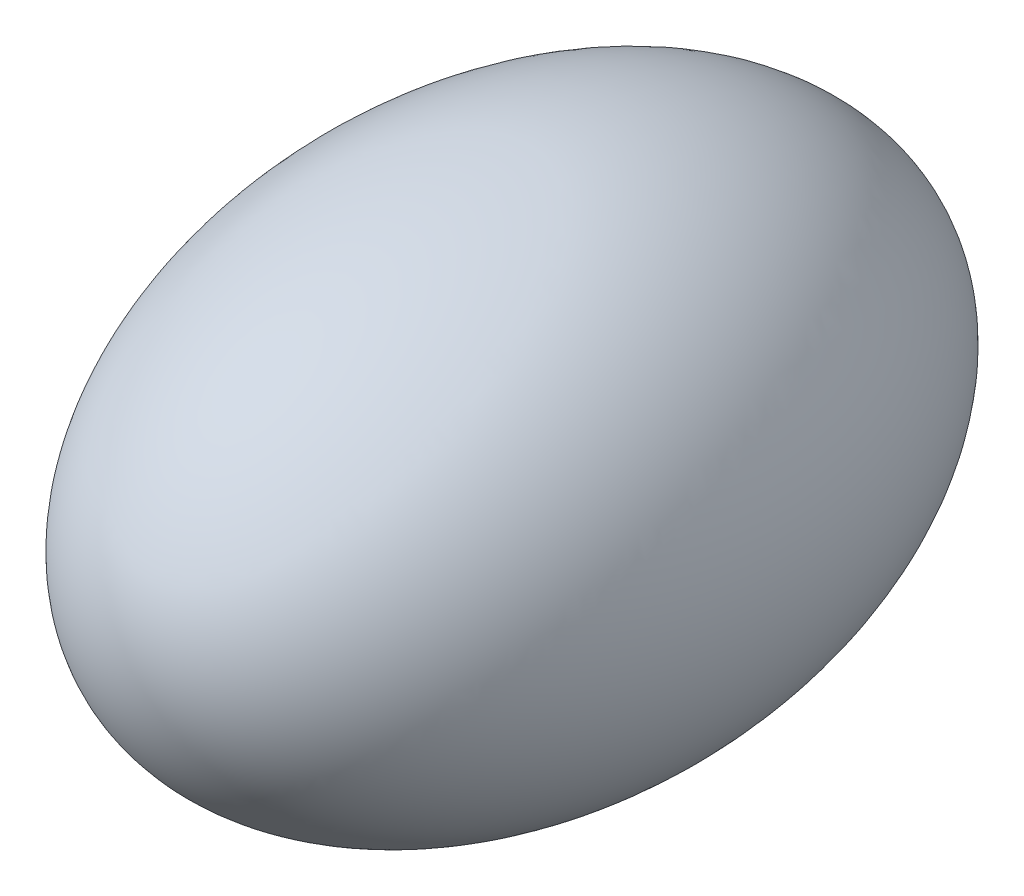
SolidWorks part; units mm, degrees
ref_plane "Front Plane" through (0, 0, 0) normal (0, 0, 1) x (1, 0, 0)
ref_plane "Top Plane" through (0, 0, 0) normal (0, 1, 0) x (1, 0, 0)
ref_plane "Right Plane" through (0, 0, 0) normal (1, 0, 0) x (0, 0, -1)
sketch "Sketch1" plane through (0, 0, 0) normal (0, 1, 0) x (1, 0, 0)
  line L0 (0, 75) -> (0, 122.057) construction
  line L1 (0, -75) -> (0, 75)
  ellipse E0 centre (0, 0) end of major axis (0, 75) minor radius 50
  dimension "D1" = 100
  dimension "D2" = 150
revolve "Revolve5" add sketch "Sketch1" angle 360 about L0 region at (21.2207, 0, 0)
